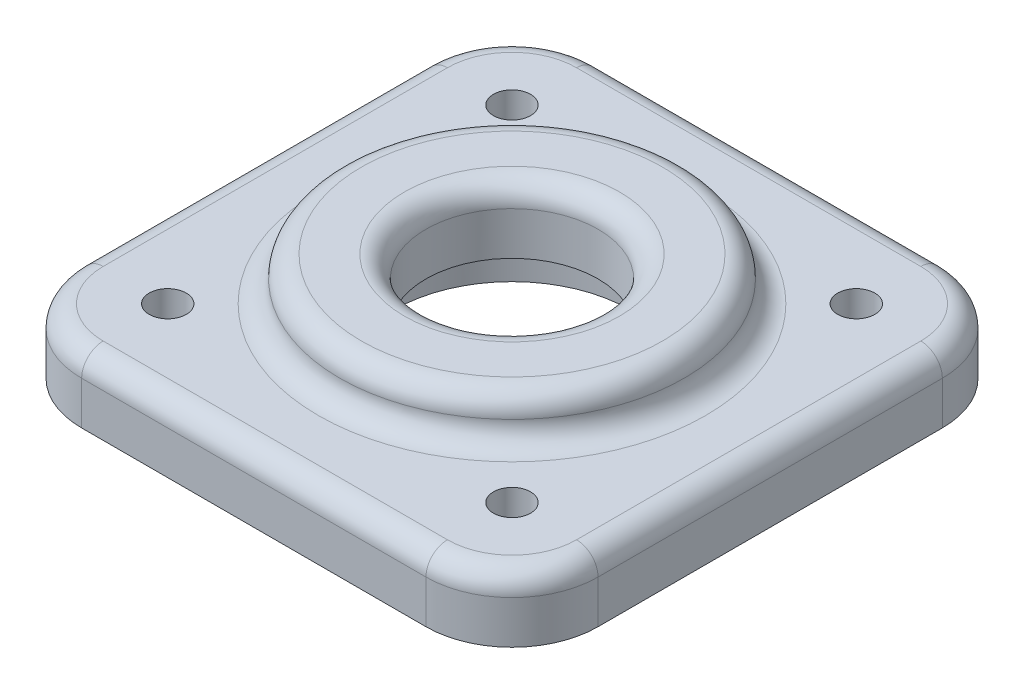
SolidWorks part; units mm, degrees
ref_plane "Front Plane" through (0, 0, 0) normal (0, 0, 1) x (1, 0, 0)
ref_plane "Top Plane" through (0, 0, 0) normal (0, 1, 0) x (1, 0, 0)
ref_plane "Right Plane" through (0, 0, 0) normal (1, 0, 0) x (0, 0, -1)
sketch "Sketch1" plane through (0, 0, 0) normal (0, 1, 0) x (1, 0, 0)
  line L1 (-8, 12) -> (8, 12)
  line L2 (-12, 8) -> (-12, -8)
  line L3 (-8, -12) -> (8, -12)
  line L4 (12, 8) -> (12, -8)
  circle A0 centre (-8, 8) radius 0.8617
  circle A1 centre (8, 8) radius 0.8617
  circle A2 centre (8, -8) radius 0.8617
  circle A3 centre (-8, -8) radius 0.8617
  circle A4 centre (0, 0) radius 5.5
  arc A5 (-8, 12) -> (-12, 8) centre (-8, 8) ccw
  arc A6 (8, 12) -> (12, 8) centre (8, 8) cw
  arc A7 (8, -12) -> (12, -8) centre (8, -8) ccw
  arc A8 (-12, -8) -> (-8, -12) centre (-8, -8) ccw
  point P2 (0, 0)
  point P13 (0, 0)
  dimension "D1" = 8
  dimension "D4" = 4
  dimension "D9" = 4
  dimension "D2" = 8
  dimension "D5" = 4
  dimension "D6" = 4
  dimension "D7" = 4
  dimension "D8" = 4
  dimension "D3" = 4
extrude "Boss-Extrude1" add sketch "Sketch1" along normal blind 3
sketch "Sketch2" plane through (0, 3, 0) normal (0, 1, 0) x (1, 0, 0)
  circle A0 centre (0, 0) radius 8
  circle A1 centre (0, 0) radius 4
extrude "Boss-Extrude2" add sketch "Sketch2" along normal blind 2
fillet "Fillet1" radius 1 11 edges at (10.8284, 3, 10.8284) (0, 3, 12) (-10.8284, 3, 10.8284) (-12, 3, 0) (-10.8284, 3, -10.8284) (0, 3, -12) (10.8284, 3, -10.8284) (0, 5, 4) (12, 3, 0) (0, 3, 8) (0, 5, 8)
ref_axis "Axis1" through (0, 3, 0) along (0, -1, 0)
sketch "Sketch3" plane through (0, 3, 0) normal (0, -1, 0) x (1, 0, 0)
  circle A0 centre (0, 0) radius 4
  circle A1 centre (0, 0) radius 5.5
extrude "Boss-Extrude3" add sketch "Sketch3" along normal blind 1
